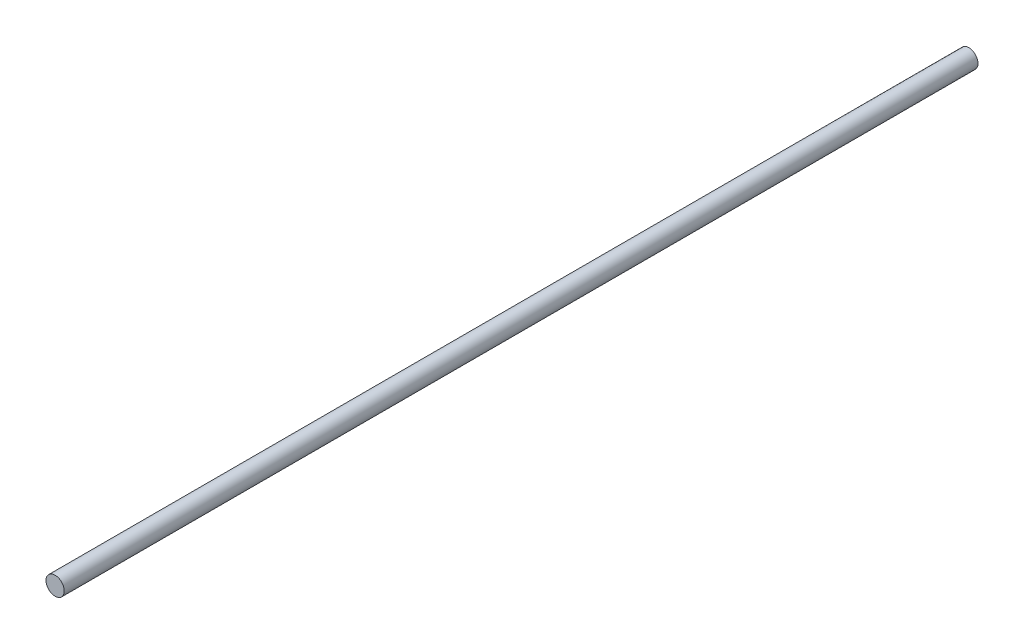
SolidWorks part; units mm, degrees
ref_plane "Front Plane" through (0, 0, 0) normal (0, 0, 1) x (1, 0, 0)
ref_plane "Top Plane" through (0, 0, 0) normal (0, 1, 0) x (1, 0, 0)
ref_plane "Right Plane" through (0, 0, 0) normal (1, 0, 0) x (0, 0, -1)
sketch "Sketch1" plane through (0, 0, 0) normal (0, 0, 1) x (1, 0, 0)
  circle A0 centre (0, 0) radius 1
extrude "Boss-Extrude1" add sketch "Sketch1" along normal blind 100 contours A0
